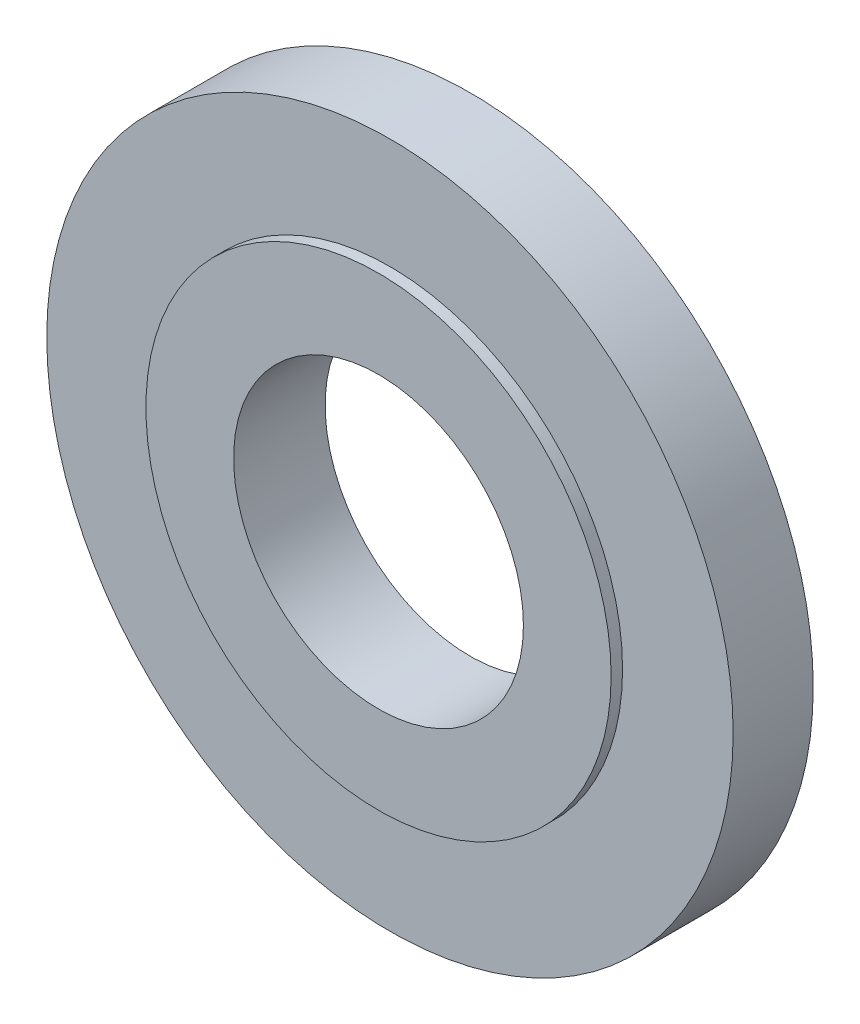
SolidWorks part; units mm, degrees
ref_plane "Спереди" through (0, 0, 0) normal (0, 0, 1) x (1, 0, 0)
ref_plane "Сверху" through (0, 0, 0) normal (0, 1, 0) x (1, 0, 0)
ref_plane "Справа" through (0, 0, 0) normal (1, 0, 0) x (0, 0, -1)
sketch "Hub Diameter" plane through (0, 0, 0) normal (0, 0, 1) x (1, 0, 0)
  circle A0 centre (0, 0) radius 61
  dimension "Diameter of Hub X" = 122
extrude "Hub" add sketch "Hub Diameter" against normal blind 24
ref_plane "Flange starting plane" through (0, 0, -3) normal (0, 0, 1) x (1, 0, 0)
sketch "Flange Diameter" plane through (0, 0, -3) normal (0, 0, 1) x (1, 0, 0)
  circle A0 centre (0, 0) radius 90
  dimension "Outside Diameter of Flange O" = 180
extrude "Flange" add sketch "Flange Diameter" against normal up to surface (21 mm away)
ref_axis "Axis of Revolution for Bore" through (0, 0, 56.9362) along (0, 0, -1)
sketch "Эскиз1" plane through (0, 0, 0) normal (0, 0, 1) x (1, 0, 0)
  circle A0 centre (0, 0) radius 38
  dimension "D1" = 76
extrude "Вырез-Вытянуть1" cut sketch "Эскиз1" against normal through all
sketch "Sketch1" plane through (0, 0, 0) normal (0, 1, 0) x (1, 0, 0)
  line L0 (0, -56.9362) -> (0, 0) construction
  line L1 (-61, 0) -> (61, 0) construction
  point P0 (0, 5)
  dimension "D1" = 5
other "CPoint1" parameters "Diameter"=65, "StubLength"=0
ref_axis "Axis1" through (0, 0, -13) along (0, 0, 1)
other "RPoint1"
